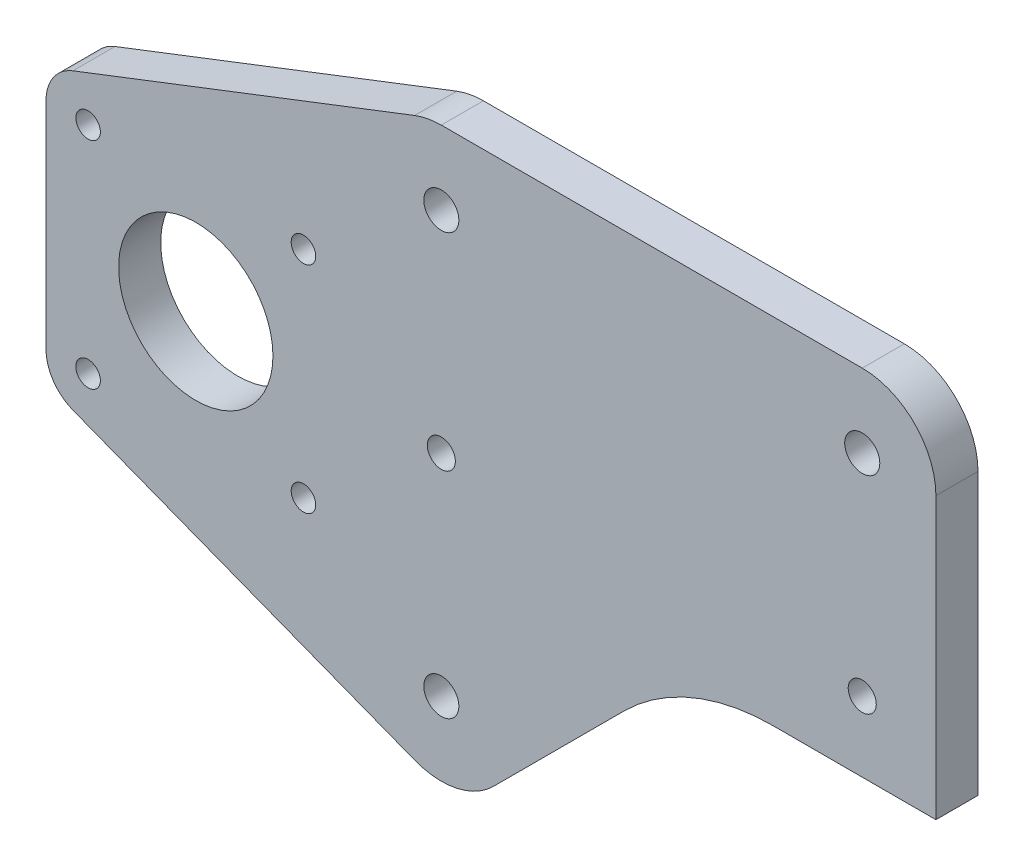
SolidWorks part; units mm, degrees
ref_plane "Plano frontal" through (0, 0, 0) normal (0, 0, 1) x (1, 0, 0)
ref_plane "Plano superior" through (0, 0, 0) normal (0, 1, 0) x (1, 0, 0)
ref_plane "Plano direito" through (0, 0, 0) normal (1, 0, 0) x (0, 0, -1)
sketch "Esboço1" plane through (0, 0, 0) normal (0, 0, 1) x (1, 0, 0)
  line L1 (-30, 30) -> (30, 30) construction
  line L2 (-30, 30) -> (-30, -30) construction
  line L3 (-30, -30) -> (30, -30) construction
  line L4 (30, 30) -> (30, -30) construction
  line L5 (-30, 30) -> (30, -30) construction
  line L6 (-30, -30) -> (30, 30) construction
  line L7 (-22.5754, -37.4246) -> (-3.9376, -18.7868)
  line L8 (30, 40.5) -> (-30, 40.5)
  line L18 (-80.3491, 15.3491) -> (-49.6509, 15.3491) construction
  line L19 (-80.3491, 15.3491) -> (-80.3491, -15.3491) construction
  line L20 (-80.3491, -15.3491) -> (-49.6509, -15.3491) construction
  line L21 (-49.6509, 15.3491) -> (-49.6509, -15.3491) construction
  line L22 (-80.3491, 15.3491) -> (-49.6509, -15.3491) construction
  line L23 (-80.3491, -15.3491) -> (-49.6509, 15.3491) construction
  line L27 (-86.3491, 15.3491) -> (-86.3491, -15.3491)
  line L28 (-33.788, -39.7929) -> (-82.5137, -20.945)
  line L29 (-33.788, 39.7929) -> (-82.5137, 20.945)
  line L30 (0, 0) -> (40.5, 0) construction
  line L31 (17.2756, -10) -> (40.5, -10)
  line L32 (0, 0) -> (40.5, 0) construction
  line L33 (40.5, 30) -> (40.5, -10)
  line L35 (0, -10) -> (40.5, -10) construction
  circle A0 centre (-30, 30) radius 2.5
  circle A1 centre (-30, -30) radius 2.5
  circle A2 centre (30, 30) radius 2.5
  arc A3 (-30, 40.5) -> (-33.788, 39.7929) centre (-30, 30) ccw
  arc A4 (-33.788, -39.7929) -> (-22.5754, -37.4246) centre (-30, -30) ccw
  arc A5 (40.5, 30) -> (30, 40.5) centre (30, 30) ccw
  circle A6 centre (-80.3491, 15.3491) radius 1.75
  circle A7 centre (30, 30) radius 10.5 construction
  circle A8 centre (-30, -30) radius 10.5 construction
  circle A9 centre (-30, 30) radius 10.5 construction
  circle A10 centre (-49.6509, 15.3491) radius 1.75
  circle A11 centre (-49.6509, -15.3491) radius 1.75
  circle A12 centre (-80.3491, -15.3491) radius 1.75
  circle A15 centre (-65, 0) radius 11
  arc A16 (-82.5137, 20.945) -> (-86.3491, 15.3491) centre (-80.3491, 15.3491) ccw
  arc A17 (-86.3491, -15.3491) -> (-82.5137, -20.945) centre (-80.3491, -15.3491) ccw
  arc A18 (17.2756, -10) -> (-3.9376, -18.7868) centre (17.2756, -40) ccw
  circle A19 centre (-30, 0) radius 2
  circle A20 centre (0, 0) radius 2 construction
  circle A21 centre (30, 0) radius 2
  point P0 (0, 0)
  point P13 (-20, 22.5)
  point P15 (-20, -22.5)
  point P20 (44, 0)
  point P23 (-65, 0)
  point P34 (-81.0386, -15.474)
  point P36 (-81.0386, 15.2242)
  point P37 (-74.2886, -15.474)
  point P43 (-74.2886, 15.2242)
  dimension "D3" = 5
  dimension "D6" = 3.5
  dimension "D8" = 22
  dimension "D11" = 30
  dimension "D12" = 4
  dimension "D1" = 60
  dimension "D2" = 60
  dimension "D5" = 60
  dimension "D9" = 35
  dimension "D7" = 6
  dimension "D13" = 30
  dimension "D4" = 8
  dimension "D10" = 10
extrude "Ressalto-extrusão1" add sketch "Esboço1" along normal blind 6
ref_axis "Eixo1" through (-30, 30, 6) along (0, 0, -1)
ref_axis "Eixo2" through (30, 30, 6) along (0, 0, -1)
ref_axis "Eixo3" through (-30, -30, 6) along (0, 0, -1)
ref_plane "Plano1" through (-30, 0, 0) normal (1, 0, 0) x (0, 0, -1)
ref_plane "Plano2" through (30, 0, 0) normal (1, 0, 0) x (0, 0, -1)
ref_plane "Plano3" through (0, 0, 0) normal (1, 0, 0) x (0, 0, -1)
ref_axis "Eixo4" through (30, 0, 6) along (0, 0, -1)
ref_axis "Eixo5" through (-30, 0, 6) along (0, 0, -1)
ref_plane "Plano4" through (0, 0, 0) normal (0, -1, 0) x (-1, 0, 0)
ref_axis "Eixo6" through (-49.6509, 15.3491, 6) along (0, 0, -1)
ref_axis "Eixo7" through (-49.6509, -15.3491, 6) along (0, 0, -1)
ref_plane "Plano5" through (-49.6509, 0, 0) normal (1, 0, 0) x (0, 0, -1)
